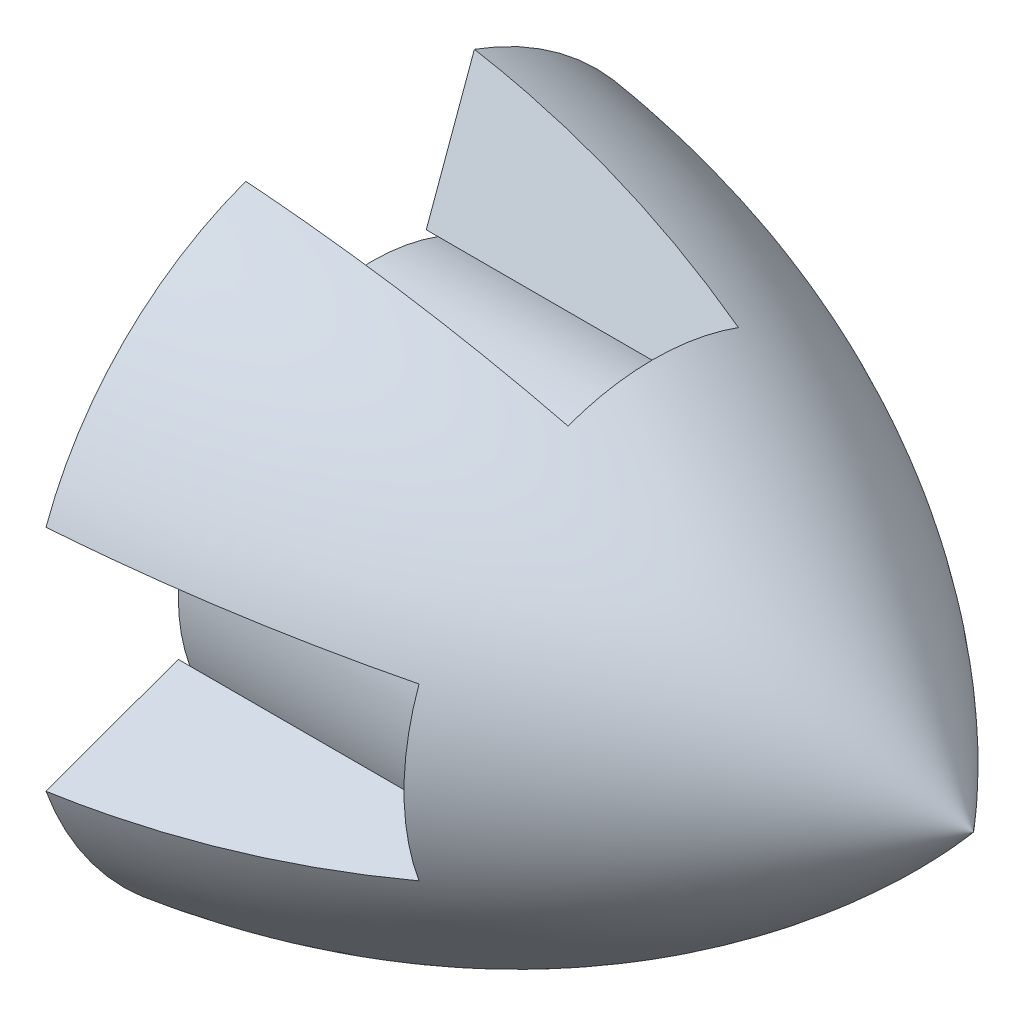
SolidWorks part; units mm, degrees
ref_plane "Спереди" through (0, 0, 0) normal (0, 0, 1) x (1, 0, 0)
ref_plane "Сверху" through (0, 0, 0) normal (0, 1, 0) x (1, 0, 0)
ref_plane "Справа" through (0, 0, 0) normal (1, 0, 0) x (0, 0, -1)
sketch "Эскиз2" plane through (0, 0, 0) normal (0, 0, 1) x (1, 0, 0)
  line L0 (0, 0) -> (0, 28.5)
  line L1 (0, 0) -> (28.5, 0)
  line L2 (-1000, 0) -> (49000, 0) construction
  line L3 (28.5, 0) -> (52.3107, 0)
  spline S0 degree 2 poles (0, 28.5) (31.309, 24.448) (52.3107, 0) knots 0 0 0 1 1 1
revolve "Повернуть1" add sketch "Эскиз2" angle 360 about L2
sketch "Эскиз7" plane through (0, 0, 0) normal (-1, 0, 0) x (0, 0, 1)
  circle A0 centre (0, 0) radius 12.6
extrude "Вырез-Вытянуть1" cut sketch "Эскиз7" against normal blind 15
sketch "Эскиз8" plane through (0, 0, 0) normal (-1, 0, 0) x (0, 0, 1)
  circle A0 centre (0, 0) radius 16.5
extrude "Вырез-Вытянуть2" cut sketch "Эскиз8" against normal blind 1
sketch "Эскиз11" plane through (0, 0, 0) normal (-1, 0, 0) x (0, 0, 1)
  line L0 (0, 0) -> (17101.0072, 46984.631) construction
  line L1 (0, 0) -> (-17101.0072, 46984.631) construction
  line L2 (-9.7476, 26.7812) -> (-5.6433, 15.5049)
  line L3 (9.7476, 26.7812) -> (5.6433, 15.5049)
  arc A0 (-5.6433, 15.5049) -> (5.6433, 15.5049) centre (0, 0) cw
  circle A1 centre (0, 0) radius 16.5 construction
  arc A2 (-9.7476, 26.7812) -> (9.7476, 26.7812) centre (0, 0) cw
  circle A3 centre (0, 0) radius 28.5 construction
extrude "Вырез-Вытянуть3" cut sketch "Эскиз11" against normal blind 25
pattern_circular "Круговой массив1" count 4 every 90 about axis through (1, 0, 0) along (-1, 0, 0) of "Вырез-Вытянуть3"
